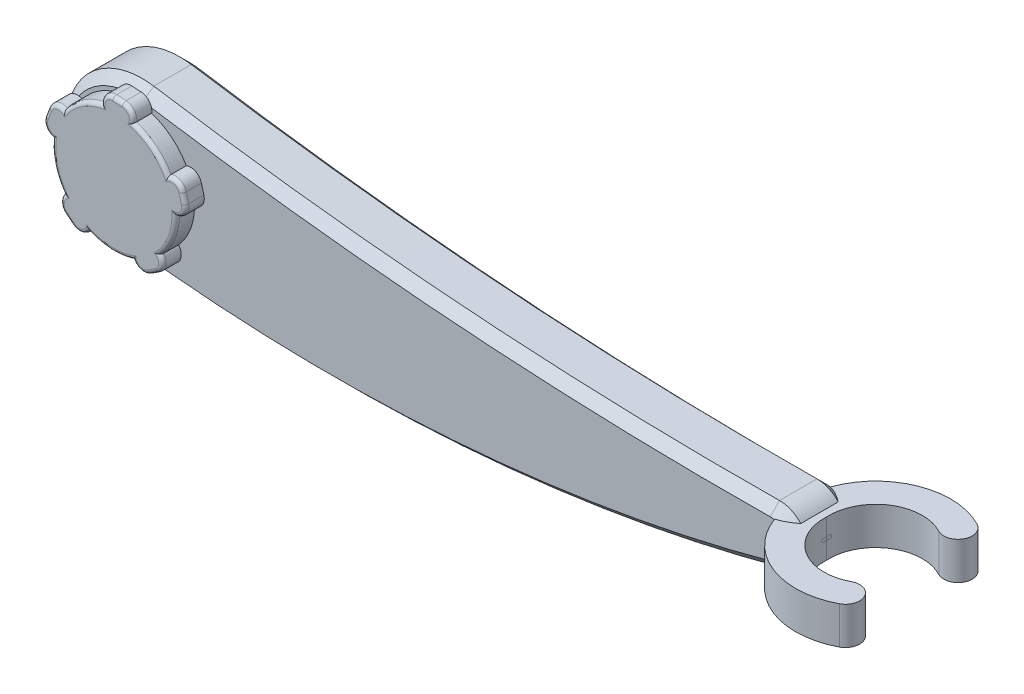
SolidWorks part; units mm, degrees
material "Plain Carbon Steel"
ref_plane "Front Plane" through (0, 0, 0) normal (0, 0, 1) x (1, 0, 0)
ref_plane "Top Plane" through (0, 0, 0) normal (0, 1, 0) x (1, 0, 0)
ref_plane "Right Plane" through (0, 0, 0) normal (1, 0, 0) x (0, 0, -1)
sketch "Sketch1" plane through (0, 0, 0) normal (0, 0, 1) x (1, 0, 0)
  line L0 (-85, 0) -> (85, 0) construction
  arc A0 (-81.8718, 19.7538) -> (-87.4615, -19.8479) centre (-85, 0) ccw
  arc A1 (86.9844, -7.2327) -> (84.9221, 7.4996) centre (85, 0) ccw
  arc A2 (-81.8718, 19.7538) -> (84.9221, 7.4996) centre (74.5404, 1007.4457) ccw
  arc A3 (-87.4615, -19.8479) -> (86.9844, -7.2327) centre (-32.0772, 426.7308) ccw
  point P4 (0, 0)
  dimension "D2" = 40
  dimension "D3" = 15
  dimension "D4" = 450
  dimension "D5" = 1000
  dimension "D1" = 170
extrude "Boss-Extrude1" add sketch "Sketch1" along normal mid plane 15
chamfer "Chamfer1" distance 2.5 angle 45 8 edges at (0.3802, -22.0971, -7.5) (92.4276, 1.0397, -7.5) (-104.8037, 2.7953, -7.5) (1.2686, 10.1337, -7.5) (0.3802, -22.0971, 7.5) (92.4276, 1.0397, 7.5) (-104.8037, 2.7953, 7.5) (1.2686, 10.1337, 7.5)
sketch "Sketch2" plane through (0, 0, 7.5) normal (0, 0, 1) x (1, 0, 0)
  circle A0 centre (-85, 0) radius 16.5
  dimension "D1" = 33
extrude "Boss-Extrude2" add sketch "Sketch2" along normal blind 5
sketch "Sketch4" plane through (0, 0, 12.5) normal (0, 0, 1) x (1, 0, 0)
  line L0 (-85, 0) -> (-68.9097, 0)
  line L1 (-66.0119, 3.7765) -> (-66.6676, 6.2235)
  line L2 (-71.0654, 8.0452) -> (-85, 0)
  line L3 (-85, 0) -> (-66.3397, 5) construction
  line L4 (-73.0426, -10.7665) -> (-85, 0)
  line L5 (-85, 0) -> (-80.0278, -15.3028)
  line L6 (-75.5407, -16.8918) -> (-73.416, -15.512)
  line L7 (-91.5445, -14.6992) -> (-85, 0)
  line L8 (-85, 0) -> (-98.0173, -9.4577)
  line L9 (-98.142, -14.2161) -> (-96.1731, -15.8105)
  line L10 (-101.0022, 1.6819) -> (-85, 0)
  line L11 (-85, 0) -> (-98.0173, 9.4577)
  line L12 (-102.5814, 8.1057) -> (-103.4893, 5.7406)
  line L13 (-88.3454, 15.7387) -> (-85, 0)
  line L14 (-85, 0) -> (-80.0278, 15.3028)
  line L15 (-82.724, 19.2257) -> (-85.2539, 19.3583)
  arc A0 (-68.9097, 0) -> (-66.0119, 3.7765) centre (-68.9097, 3) ccw
  arc A1 (-71.0654, 8.0452) -> (-66.6676, 6.2235) centre (-69.5654, 5.4471) cw
  arc A2 (-73.0426, -10.7665) -> (-73.416, -15.512) centre (-75.05, -12.996) cw
  arc A3 (-80.0278, -15.3028) -> (-75.5407, -16.8918) centre (-77.1746, -14.3758) ccw
  arc A4 (-91.5445, -14.6992) -> (-96.1731, -15.8105) centre (-94.2852, -13.479) cw
  arc A5 (-98.0173, -9.4577) -> (-98.142, -14.2161) centre (-96.254, -11.8847) ccw
  arc A6 (-101.0022, 1.6819) -> (-103.4893, 5.7406) centre (-100.6886, 4.6655) cw
  arc A7 (-98.0173, 9.4577) -> (-102.5814, 8.1057) centre (-99.7807, 7.0306) ccw
  arc A8 (-88.3454, 15.7387) -> (-85.2539, 19.3583) centre (-85.4109, 16.3624) cw
  arc A9 (-80.0278, 15.3028) -> (-82.724, 19.2257) centre (-82.881, 16.2299) ccw
  point P10 (-67.6795, 10)
  point P37 (-85, 0)
  circle M22 centre (-85, 0) radius 16.5
  dimension "D3" = 3
  dimension "D1" = 30
  dimension "D2" = 20
  dimension "D4" = 5
extrude "Boss-Extrude3" add sketch "Sketch4" along direction (0, 0, 1) on the side against the normal blind 5 contours A9 L15 A8 M22 | L3 L1 A1 M22 | L3 A0 L1 M22 | A3 L6 A2 M22 | A5 L9 A4 M22 | A7 L12 A6 M22 region at (-68.4431, 6.4563, 12.5) region at (-67.4332, 2.6871, 12.5) region at (-75.3796, -14.8141, 12.5) region at (-96.1162, -13.7273, 12.5) region at (-101.4905, 6.3301, 12.5) region at (-84.0756, 17.6395, 12.5)
fillet "Fillet2" radius 1 20 edges at (-87.5535, 18.4623, 12.5) (-83.9889, 19.292, 12.5) (-80.5307, 18.0943, 12.5) (-74.6162, 12.8229, 12.5) (-68.2303, 8.1337, 12.5) (-66.3397, 5, 12.5) (-66.4102, 1.3409, 12.5) (-69.5959, -5.9131, 12.5) (-72.0823, -13.4355, 12.5) (-74.4784, -16.2019, 12.5) (-77.9802, -17.2656, 12.5) (-85.8635, -16.4774, 12.5) (-93.7861, -16.4372, 12.5) (-97.1575, -15.0133, 12.5) (-99.2513, -12.0116, 12.5) (-100.9378, -4.2705, 12.5) (-103.3478, 3.2767, 12.5) (-103.0354, 6.9231, 12.5) (-100.8276, 9.842, 12.5) (-93.9865, 13.8381, 12.5)
sketch "Sketch6" plane through (0, 0, -7.5) normal (0, 0, -1) x (-1, 0, 0)
  circle A0 centre (85, 0) radius 5
  dimension "D1" = 10
extrude "Boss-Extrude4" add sketch "Sketch6" along normal blind 10
sketch "Sketch7" plane through (0, 0, 0) normal (0, 1, 0) x (1, 0, 0)
  line L0 (92.5, 0) -> (0, 0) construction
  line L1 (92.5, -5) -> (92.5, 5) construction
  line L3 (84.9221, -5) -> (84.9221, 5) construction
  arc A0 (84.9221, 0) -> (114.2718, 18.3453) centre (104.9109, 0.6712) cw
  arc A1 (92.5, 0) -> (110.7282, 11.6547) centre (104.9109, 0.6712) cw
  arc A2 (114.2718, 18.3453) -> (110.7282, 11.6547) centre (112.5, 15) cw
  arc A3 (92.5, 0) -> (110.7282, -11.6547) centre (104.9109, -0.6712) ccw
  arc A4 (114.2718, -18.3453) -> (110.7282, -11.6547) centre (112.5, -15) ccw
  arc A5 (84.9221, 0) -> (114.2718, -18.3453) centre (104.9109, -0.6712) ccw
  dimension "D1" = 20
  dimension "D3" = 15
  dimension "D4" = 20
extrude "Boss-Extrude5" add sketch "Sketch7" along normal mid plane 10
